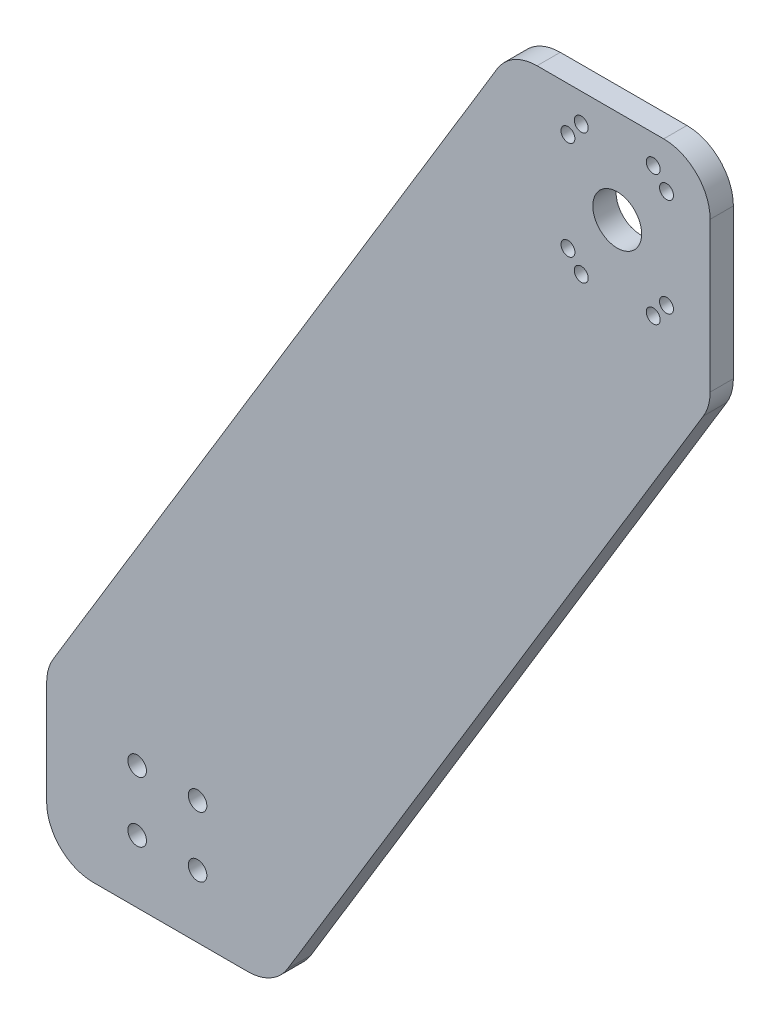
SolidWorks part; units mm, degrees
ref_plane "Piano frontale" through (0, 0, 0) normal (0, 0, 1) x (1, 0, 0)
ref_plane "Piano superiore" through (0, 0, 0) normal (0, 1, 0) x (1, 0, 0)
ref_plane "Piano destro" through (0, 0, 0) normal (1, 0, 0) x (0, 0, -1)
sketch "Schizzo1" plane through (0, 0, 0) normal (0, 0, 1) x (1, 0, 0)
  line L0 (20, 0) -> (86.6282, 0)
  line L1 (103.7355, 9.6395) -> (282.7476, 305.2236)
  line L2 (285.6403, 315.5841) -> (285.6403, 380)
  line L3 (265.6403, 400) -> (211.1245, 400)
  line L4 (0, 64.4159) -> (0, 20)
  line L5 (194.0172, 390.3605) -> (2.8927, 74.7764)
  line L6 (267.7327, 396.2552) -> (-16.2489, -72.6542) construction
  line L7 (11.1965, 40) -> (107.4959, 40) construction
  line L8 (51.9769, 40) -> (51.9769, 85.084) construction
  line L9 (245.6403, 359.7762) -> (217.1497, 388.2668) construction
  line L10 (245.6403, 359.7762) -> (207.2912, 359.7762) construction
  line L11 (245.6403, 359.7762) -> (245.6403, 402.6918) construction
  line L13 (261.1403, 331.7762) -> (230.1403, 331.7762) construction
  line L14 (261.1403, 331.7762) -> (261.1403, 387.7762) construction
  line L15 (261.1403, 387.7762) -> (230.1403, 387.7762) construction
  line L16 (230.1403, 331.7762) -> (230.1403, 387.7762) construction
  line L17 (261.1403, 331.7762) -> (230.1403, 387.7762) construction
  line L18 (261.1403, 387.7762) -> (230.1403, 331.7762) construction
  circle A0 centre (38.9769, 53) radius 4
  circle A1 centre (64.9769, 53) radius 4
  circle A2 centre (64.9769, 27) radius 4
  circle A3 centre (38.9769, 27) radius 4
  circle A4 centre (245.6403, 359.7762) radius 10.5
  circle A5 centre (245.6403, 359.7762) radius 30 construction
  arc A6 (103.7355, 9.6395) -> (86.6282, 0) centre (86.6282, 20) cw
  arc A7 (20, 0) -> (0, 20) centre (20, 20) cw
  arc A8 (0, 64.4159) -> (2.8927, 74.7764) centre (20, 64.4159) cw
  arc A9 (285.6403, 315.5841) -> (282.7476, 305.2236) centre (265.6403, 315.5841) cw
  arc A10 (285.6403, 380) -> (265.6403, 400) centre (265.6403, 380) ccw
  arc A11 (211.1245, 400) -> (194.0172, 390.3605) centre (211.1245, 380) ccw
  circle A12 centre (230.1403, 387.7762) radius 3
  circle A13 centre (261.1403, 387.7762) radius 3
  circle A14 centre (266.8535, 380.9894) radius 3
  circle A15 centre (266.8535, 338.563) radius 3
  circle A16 centre (261.1403, 331.7762) radius 3
  circle A17 centre (230.1403, 331.7762) radius 3
  circle A18 centre (224.4271, 338.563) radius 3
  circle A19 centre (224.4271, 380.9894) radius 3
  point P27 (224.4271, 380.9894)
  point P28 (266.8535, 380.9894)
  point P29 (266.8535, 338.563)
  point P30 (224.4271, 338.563)
  point P39 (0, 0)
  point P42 (0, 70)
  point P45 (285.6403, 310)
  point P48 (285.6403, 400)
  dimension "D6" = 8
  dimension "D7" = 13
  dimension "D9" = 21
  dimension "D11" = 45
  dimension "D14" = 20
  dimension "D15" = 6
  dimension "D16" = 40
  dimension "D17" = 60
  dimension "D1" = 121.2
  dimension "D2" = 120
  dimension "D3" = 70
  dimension "D4" = 400
  dimension "D5" = 90
  dimension "D8" = 13
  dimension "D10" = 40
  dimension "D12" = 31
  dimension "D13" = 56
extrude "Estrusione-Estrusione2" add sketch "Schizzo1" against normal blind 10
sketch "Schizzo2" plane through (0, 0, 0) normal (0, -1, 0) x (1, 0, 0)
  line L0 (20, -5) -> (86.6282, -5) construction
  line L1 (20, -10) -> (20, 0) construction
  line L2 (86.6282, -10) -> (86.6282, 0) construction
  line L3 (53.3141, -5) -> (53.3141, 0) construction
  line L4 (20, 0) -> (86.6282, 0) construction
  circle A0 centre (53.3141, -5) radius 2
  circle A1 centre (80.8141, -5) radius 2
  circle A2 centre (25.8141, -5) radius 2
  dimension "D1" = 4
  dimension "D2" = 27.5
extrude "Taglio-Estrusione1" cut sketch "Schizzo2" against normal blind 15
